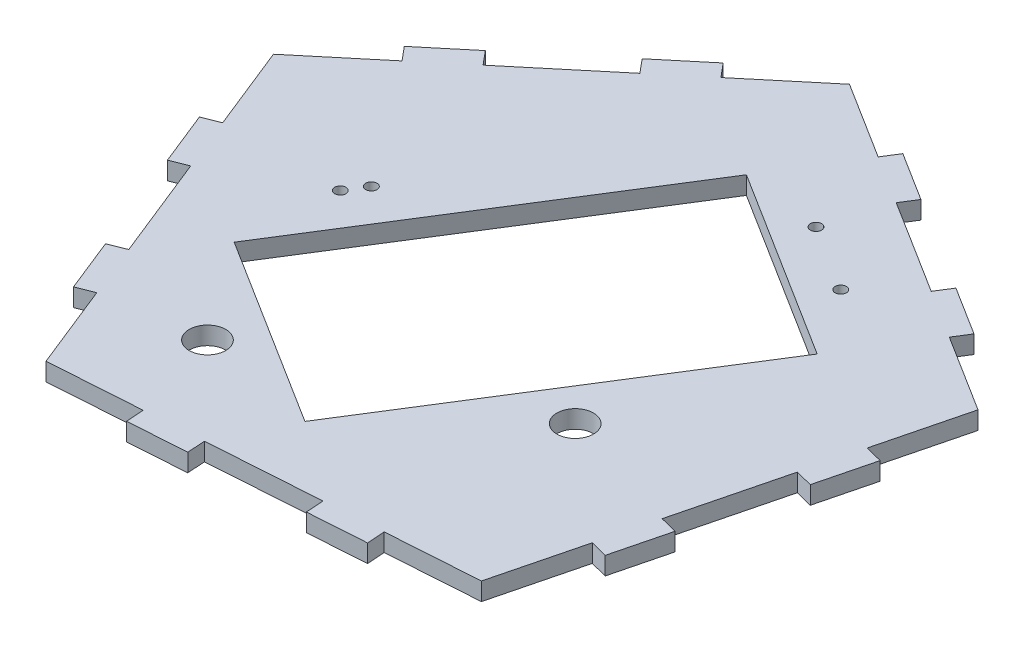
SolidWorks part; units mm, degrees
ref_plane "Front Plane" through (0, 0, 0) normal (0, 0, 1) x (1, 0, 0)
ref_plane "Top Plane" through (0, 0, 0) normal (0, 1, 0) x (1, 0, 0)
ref_plane "Right Plane" through (0, 0, 0) normal (1, 0, 0) x (0, 0, -1)
sketch "Sketch1" plane through (0, 0, 0) normal (0, 1, 0) x (1, 0, 0)
  line L1 (-59.9258, 15.1181) -> (-32.8962, -52.3211)
  line L2 (-32.8962, -52.3211) -> (39.5948, -47.4543)
  line L3 (39.5948, -47.4543) -> (57.3672, 22.9927)
  line L4 (57.3672, 22.9927) -> (-4.14, 61.6646)
  line L5 (-4.14, 61.6646) -> (-59.9258, 15.1181)
  circle A0 centre (0, 0) radius 50 construction
  dimension "D1" = 100
extrude "Boss-Extrude1" add sketch "Sketch1" along normal blind 3.18
ref_axis "Axis" through (0, 3.339, 0) along (0, -1, 0)
sketch "Axis Check" plane through (0, 3.18, 0) normal (0, 1, 0) x (1, 0, 0)
  line L0 (3.3493, -49.8877) -> (-4.14, 61.6646) construction
  line L1 (-32.8962, -52.3211) -> (39.5948, -47.4543) construction
  line L2 (57.3672, 22.9927) -> (-46.411, -18.6015) construction
  line L3 (-59.9258, 15.1181) -> (-32.8962, -52.3211) construction
  line L4 (-32.0329, 38.3913) -> (39.5948, -47.4543) construction
  line L5 (-4.14, 61.6646) -> (-59.9258, 15.1181) construction
  line L6 (-59.9258, 15.1181) -> (48.481, -12.2308) construction
  line L7 (39.5948, -47.4543) -> (57.3672, 22.9927) construction
  line L8 (-32.8962, -52.3211) -> (26.6136, 42.3287) construction
  line L9 (57.3672, 22.9927) -> (-4.14, 61.6646) construction
sketch "Sketch2" plane through (0, 0, 0) normal (0, -1, 0) x (1, 0, 0)
  line L0 (-53.8107, 0.1392) -> (-50.859, -1.0438)
  line L1 (-53.8107, 0.1392) -> (-50.1723, 9.2172)
  line L2 (-50.859, -1.0438) -> (-47.2205, 8.0342)
  line L3 (-50.1723, 9.2172) -> (-47.2205, 8.0342)
  line L4 (-59.9258, -15.1181) -> (-32.8962, 52.3211) construction
  line L5 (-42.6498, 27.9858) -> (-39.0113, 37.0638)
  line L6 (-42.6498, 27.9858) -> (-39.6981, 26.8028)
  line L7 (-39.0113, 37.0638) -> (-36.0596, 35.8808)
  line L8 (-39.6981, 26.8028) -> (-36.0596, 35.8808)
  line L9 (-46.411, 18.6015) -> (-19.2439, 7.7129) construction
  line L10 (-40.8306, 32.5248) -> (-37.8788, 31.3418) construction
  dimension "D1" = 3.18
  dimension "D2" = 9.78
  dimension "D3" = 10.11
extrude "Cut F" [suppressed] cut sketch "Sketch2" against normal through all
sketch "Sketch4" plane through (0, 3.18, 0) normal (0, 1, 0) x (1, 0, 0)
  line L9 (26.6136, 42.3287) -> (-26.6136, -42.3287) construction
  line L10 (57.3672, 22.9927) -> (-4.14, 61.6646) construction
  line L11 (-34.4964, -17.2915) -> (0.6335, 38.5824)
  line L12 (-34.4964, -17.2915) -> (-0.6335, -38.5824)
  line L13 (0.6335, 38.5824) -> (34.4964, 17.2915)
  line L14 (-0.6335, -38.5824) -> (34.4964, 17.2915)
  line L15 (-34.4964, -17.2915) -> (34.4964, 17.2915) construction
  line L16 (0.6335, 38.5824) -> (-0.6335, -38.5824) construction
  line L20 (0, 0) -> (39.0006, -24.5211) construction
  circle A0 centre (-21.8232, -34.7095) radius 3.25
  circle A1 centre (23.7041, -14.9036) radius 3.25
  point P5 (0, 0)
  point P6 (-21.8232, -34.7095)
  dimension "D3" = 6.5
  dimension "D1" = 40
  dimension "D2" = 66
  dimension "D4" = 8
  dimension "D5" = 8
extrude "Top Cut" cut sketch "Sketch4" against normal blind 10
sketch "Sketch7" plane through (0, 3.18, 0) normal (0, 1, 0) x (1, 0, 0)
  line L0 (0, 0) -> (26.6136, 42.3287) construction
  line L1 (57.3672, 22.9927) -> (-4.14, 61.6646) construction
  line L2 (-7.1857, -11.4287) -> (-30.8897, 3.4749) construction
  line L3 (-14.3588, -11.6437) -> (-33.0188, 0.0886) construction
  line L5 (0.6335, 38.5824) -> (-34.4964, -17.2915) construction
  circle A0 centre (-30.8897, 3.4749) radius 1
  circle A1 centre (-33.0188, 0.0886) radius 1
  dimension "D5" = 2
  dimension "D1" = 4
  dimension "D2" = 17.5
  dimension "D3" = 8
  dimension "D4" = 8
extrude "Top Cut 2" cut sketch "Sketch7" against normal through all
sketch "Sketch10" plane through (0, 3.18, 0) normal (0, 1, 0) x (1, 0, 0)
  line L0 (26.6136, 42.3287) -> (17.565, 27.9369) construction
  line L1 (57.3672, 22.9927) -> (-4.14, 61.6646) construction
  line L2 (34.4964, 17.2915) -> (0.6335, 38.5824) construction
  line L3 (30.1304, 27.124) -> (10.6872, 39.3486) construction
  circle A0 centre (14.8326, 36.7423) radius 1
  circle A1 centre (26.6846, 29.2905) radius 1
  dimension "D1" = 6
  dimension "D2" = 2
  dimension "D3" = 7
extrude "Top Cut 3" cut sketch "Sketch10" against normal blind 10
sketch "Sketch8" [suppressed] plane through (0, 3.18, 0) normal (0, 1, 0) x (1, 0, 0)
  line L0 (3.3493, -49.8877) -> (-4.14, 61.6646) construction
  line L5 (-32.8962, -52.3211) -> (39.5948, -47.4543) construction
  line L6 (-17.9455, -31.2723) -> (21.9647, -28.5929)
  line L11 (-17.9455, -31.2723) -> (-21.9647, 28.5929)
  line L12 (21.9647, -28.5929) -> (17.9455, 31.2723)
  line L13 (-21.9647, 28.5929) -> (17.9455, 31.2723)
  point P4 (1.4955, -22.2759)
  dimension "D1" = 60
  dimension "D2" = 40
  dimension "D3" = 20
extrude "Bottom Cut" [suppressed] cut sketch "Sketch8" against normal blind 10
sketch "Sketch9" [suppressed] plane through (0, 3.18, 0) normal (0, 1, 0) x (1, 0, 0)
  line L0 (19.9551, 1.3397) -> (-19.9551, -1.3397) construction
  line L1 (21.9647, -28.5929) -> (17.9455, 31.2723) construction
  line L2 (-21.9647, 28.5929) -> (-17.9455, -31.2723) construction
  line L3 (-19.9551, -1.3397) -> (-44.4689, -2.9855) construction
  line L4 (19.9551, 1.3397) -> (42.6839, 2.8657) construction
  line L5 (-32.8962, -52.3211) -> (39.5948, -47.4543) construction
  line L6 (-29.6051, -6.8886) -> (-32.3788, -7.0748)
  line L7 (-29.6051, -6.8886) -> (-30.2602, 2.8694)
  line L8 (-30.2602, 2.8694) -> (-33.0339, 2.6832)
  line L9 (-32.3788, -7.0748) -> (-33.0339, 2.6832)
  line L10 (-29.6051, -6.8886) -> (-33.0339, 2.6832) construction
  line L11 (-30.2602, 2.8694) -> (-32.3788, -7.0748) construction
  line L12 (33.0339, -2.6832) -> (30.2602, -2.8694)
  line L13 (33.0339, -2.6832) -> (32.3788, 7.0748)
  line L14 (32.3788, 7.0748) -> (29.6051, 6.8886)
  line L15 (30.2602, -2.8694) -> (29.6051, 6.8886)
  line L16 (33.0339, -2.6832) -> (29.6051, 6.8886) construction
  line L17 (32.3788, 7.0748) -> (30.2602, -2.8694) construction
  line L18 (-32.8962, -52.3211) -> (39.5948, -47.4543) construction
  point P6 (-31.3195, -2.1027)
  point P13 (31.3195, 2.1027)
  dimension "D1" = 9.78
  dimension "D4" = 9.78
  dimension "D5" = 10
  dimension "D6" = 10
  dimension "D2" = 2.78
  dimension "D3" = 2.78
extrude "Battery Holder Cut" [suppressed] cut sketch "Sketch9" against normal blind 3.18
sketch "Sketch3" plane through (0, 3.18, 0) normal (0, 1, 0) x (1, 0, 0)
  line L0 (0, 0) -> (-40.9819, 49.1167) construction
  line L1 (-49.5112, 27.9494) -> (-45.4366, 23.066)
  line L3 (-45.4366, 23.066) -> (-37.5894, 29.6135)
  line L4 (-41.664, 34.4969) -> (-37.5894, 29.6135)
  line L5 (-4.14, 61.6646) -> (-59.9258, 15.1181) construction
  line L6 (-71.9961, 5.0469) -> (-69.9588, 2.6052)
  line L7 (-71.9961, 5.0469) -> (-47.4739, 25.5077)
  line L14 (-26.4764, 47.1691) -> (-22.4018, 42.2857)
  line L16 (-22.4018, 42.2857) -> (-14.5546, 48.8333)
  line L17 (-18.6292, 53.7166) -> (-14.5546, 48.8333)
  line L18 (-42.539, 27.5695) -> (-41.513, 26.3398) construction
  line L19 (-49.5112, 27.9494) -> (-41.664, 34.4969)
  line L21 (-26.4764, 47.1691) -> (-18.6292, 53.7166)
  line L22 (-16.5919, 51.275) -> (4.7866, 69.1127)
  line L23 (-39.6267, 32.0552) -> (-24.4391, 44.7274)
  line M18 (-4.14, 61.6646) -> (-59.9258, 15.1181)
  dimension "D1" = 3.18
  dimension "D2" = 10.22
  dimension "D3" = 9.89
  dimension "D4" = 100
extrude "Extrude M" add sketch "Sketch3" against normal up to surface (3.18 mm away) contours L21 L14 L7 L17 | L19 L1 L4 M18 region at (-44.5689, 3.18, -30.0023) region at (-21.5341, 3.18, -49.222) up to face at (14.8326, 0, -35.7423)
pattern_circular "Circle F" [suppressed] count 5 over 360 about axis through (0, 3.339, 0) along (0, -1, 0) of bodies 173
pattern_circular "Circle M" count 5 over 360 about axis through (0, 3.339, 0) along (0, -1, 0) of "Extrude M"
pattern_circular "Circle Side F" [suppressed] count 5 over 360 about axis through (0, 3.339, 0) along (0, -1, 0) of bodies 173
pattern_circular "Circle Side M" [suppressed] count 5 over 360 about axis through (0, 3.339, 0) along (0, -1, 0) of bodies 168
equation "\"kerf\"= .22mm"
equation "\"tabWidthF\"= 10 - \"kerf\""
equation "\"tabThickness\"= 3.18"
equation "\"D1@Sketch2\"=\"tabThickness\""
equation "\"tabWidthM\"= 10 + \"kerf\""
equation "\"halfkerf\"= \"kerf\" / 2.00mm"
equation "\"D1@Sketch9\"=\"tabWidthF\""
equation "\"D4@Sketch9\"=\"tabWidthF\""
equation "\"D1@Battery Holder Cut\" = \"tabThickness\""
equation "\"tabLength\" = \"kerf\" + 12"
